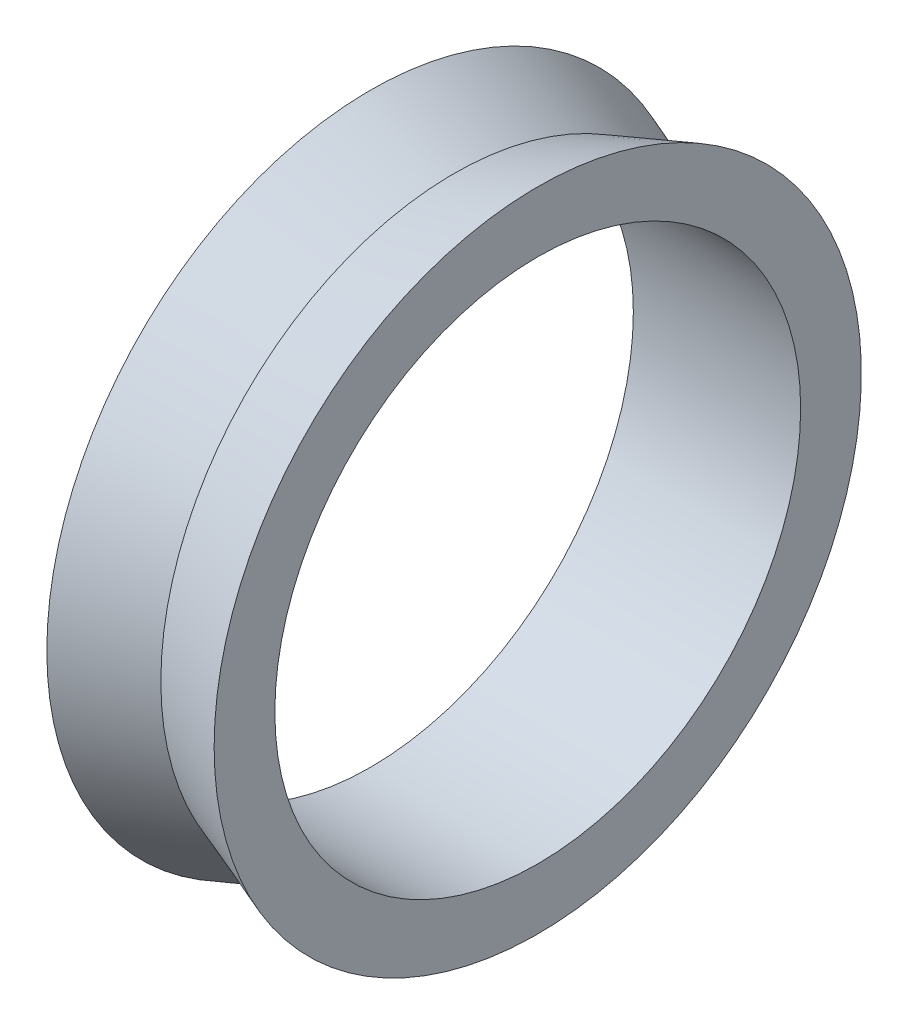
SolidWorks part; units mm, degrees
ref_plane "Front Plane" through (0, 0, 0) normal (0, 0, 1) x (1, 0, 0)
ref_plane "Top Plane" through (0, 0, 0) normal (0, 1, 0) x (1, 0, 0)
ref_plane "Right Plane" through (0, 0, 0) normal (1, 0, 0) x (0, 0, -1)
sketch "Sketch1" plane through (0, 0, 0) normal (0, 0, 1) x (1, 0, 0)
  line L0 (-3.5, 11) -> (3.5, 11)
  line L1 (0, 11) -> (0, 0) construction
  line L2 (-3.5, 11) -> (-3.5, 13.54)
  line L3 (-3.5, 13.54) -> (0, 12.27)
  line L4 (3.5, 13.54) -> (0, 12.27)
  line L5 (3.5, 11) -> (3.5, 13.54)
  line L6 (0, 0) -> (9.4357, 0)
  line L7 (55, 0) -> (-55, 0) construction
  dimension "D1" = 7
  dimension "D2" = 11
  dimension "D3" = 2.54
  dimension "D4" = 1.27
revolve "Revolve1" add sketch "Sketch1" angle 360 about L6 region at (0, 11.9878, 0)
